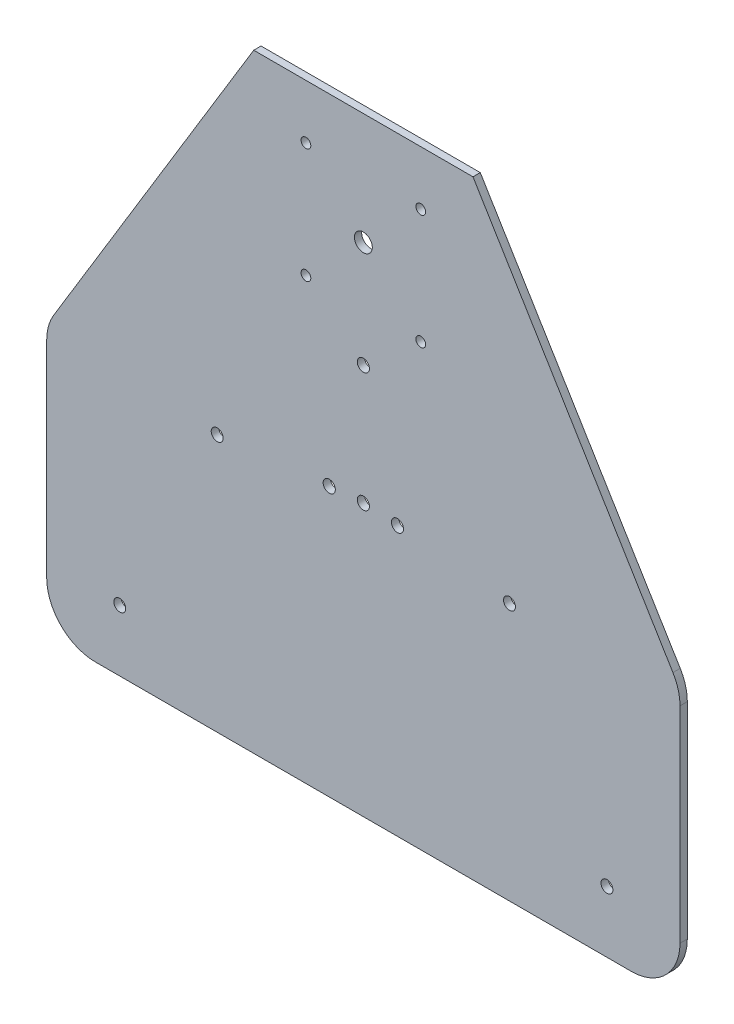
SolidWorks part; units mm, degrees
ref_plane "Alzado" through (0, 0, 0) normal (0, 0, 1) x (1, 0, 0)
ref_plane "Planta" through (0, 0, 0) normal (0, 1, 0) x (1, 0, 0)
ref_plane "Vista lateral" through (0, 0, 0) normal (1, 0, 0) x (0, 0, -1)
sketch "Croquis1" plane through (0, 0, 0) normal (0, 0, 1) x (1, 0, 0)
  line L0 (0, -28.2) -> (0, -108.2) construction
  line L1 (-23.57, -23.57) -> (23.57, -23.57) construction
  line L2 (-23.57, -23.57) -> (-23.57, 23.57) construction
  line L3 (-23.57, 23.57) -> (23.57, 23.57) construction
  line L4 (23.57, -23.57) -> (23.57, 23.57) construction
  line L5 (-23.57, -23.57) -> (23.57, 23.57) construction
  line L6 (-23.57, 23.57) -> (23.57, -23.57) construction
  line L7 (-28.2, -28.2) -> (28.2, -28.2) construction
  line L8 (-28.2, -28.2) -> (-28.2, 28.2) construction
  line L9 (-28.2, 28.2) -> (28.2, 28.2) construction
  line L10 (28.2, -28.2) -> (28.2, 28.2) construction
  line L11 (-28.2, -28.2) -> (28.2, 28.2) construction
  line L12 (-28.2, 28.2) -> (28.2, -28.2) construction
  line L13 (0, -28.2) -> (30.1, -28.2) construction
  line L14 (0, -108.2) -> (0, -169.2) construction
  line L15 (-30.1, -108.2) -> (30.1, -108.2) construction
  line L16 (-30.1, -108.2) -> (-30.1, -28.2) construction
  line L17 (-30.1, -28.2) -> (30.1, -28.2) construction
  line L18 (30.1, -108.2) -> (30.1, -28.2) construction
  line L19 (-30.1, -108.2) -> (30.1, -28.2) construction
  line L20 (-30.1, -28.2) -> (30.1, -108.2) construction
  line L21 (-14, -108.7) -> (-14, -93.7) construction
  line L22 (-221.5898, -108.7) -> (221.5898, -108.7) construction
  line L23 (-221.5898, -108.7) -> (-221.5898, -168.7) construction
  line L24 (-221.5898, -168.7) -> (221.5898, -168.7) construction
  line L25 (221.5898, -108.7) -> (221.5898, -168.7) construction
  line L26 (-221.5898, -108.7) -> (221.5898, -168.7) construction
  line L27 (-221.5898, -168.7) -> (221.5898, -108.7) construction
  line L28 (-221.5898, -122.2) -> (221.5898, -122.2) construction
  line L29 (-221.5898, -138.7) -> (221.5898, -138.7) construction
  line L30 (0, -169.2) -> (0, -204.2) construction
  line L31 (-130, -204.2) -> (130, -204.2)
  line L32 (130, -204.2) -> (130, -94.2)
  line L33 (130, -94.2) -> (45, 45.8)
  line L34 (45, 45.8) -> (-45, 45.8)
  line L35 (0, 45.8) -> (0, -169.2) construction
  line L36 (-130, -204.2) -> (-130, -94.2)
  line L37 (-130, -94.2) -> (-45, 45.8)
  circle A0 centre (-23.57, 23.57) radius 2
  circle A1 centre (23.57, 23.57) radius 2
  circle A2 centre (-23.57, -23.57) radius 2
  circle A3 centre (23.57, -23.57) radius 2
  circle A4 centre (0, 0) radius 3.675
  circle A5 centre (-14, -93.7) radius 6 construction
  circle A6 centre (14, -93.7) radius 6 construction
  circle A7 centre (-14, -93.7) radius 2.5
  circle A8 centre (14, -93.7) radius 2.5
  circle A9 centre (0, 0) radius 8 construction
  circle A10 centre (-60, -98.4) radius 12 construction
  circle A11 centre (-60, -98.4) radius 2.45
  circle A12 centre (60, -98.4) radius 12 construction
  circle A13 centre (60, -98.4) radius 2.45
  circle A14 centre (-100, -179) radius 12 construction
  circle A15 centre (-100, -179) radius 2.45
  circle A16 centre (100, -179) radius 2.45
  circle A17 centre (100, -179) radius 12 construction
  circle A18 centre (0, -43.7) radius 2.5
  circle A19 centre (0, -92.7) radius 2.5
  point P0 (0, 0)
  point P10 (0, 0)
  point P19 (0, -68.2)
  point P21 (0, -138.7)
  dimension "D3" = 4
  dimension "D4" = 4
  dimension "D5" = 4
  dimension "D6" = 4
  dimension "D9" = 7.35
  dimension "D16" = 12
  dimension "D17" = 5
  dimension "D18" = 16
  dimension "D19" = 10.3
  dimension "D20" = 24
  dimension "D22" = 4.9
  dimension "D24" = 24
  dimension "D25" = 4.9
  dimension "D32" = 5
  dimension "D33" = 5
  dimension "D1" = 47.14
  dimension "D2" = 47.14
  dimension "D7" = 56.4
  dimension "D8" = 56.4
  dimension "D10" = 80
  dimension "D11" = 30.1
  dimension "D12" = 61
  dimension "D13" = 13.5
  dimension "D14" = 14
  dimension "D15" = 15
  dimension "D21" = 60
  dimension "D23" = 10.3
  dimension "D26" = 100
  dimension "D27" = 130
  dimension "D28" = 35
  dimension "D29" = 110
  dimension "D30" = 45
  dimension "D31" = 250
  dimension "D34" = 15.5
  dimension "D35" = 15.5
extrude "Saliente-Extruir1" add sketch "Croquis1" along normal blind 3
fillet "Redondeo1" radius 20 2 edges at (-130, -204.2, 1.5) (130, -204.2, 1.5)
fillet "Redondeo2" radius 20 2 edges at (130, -94.2, 1.5) (-130, -94.2, 1.5)
